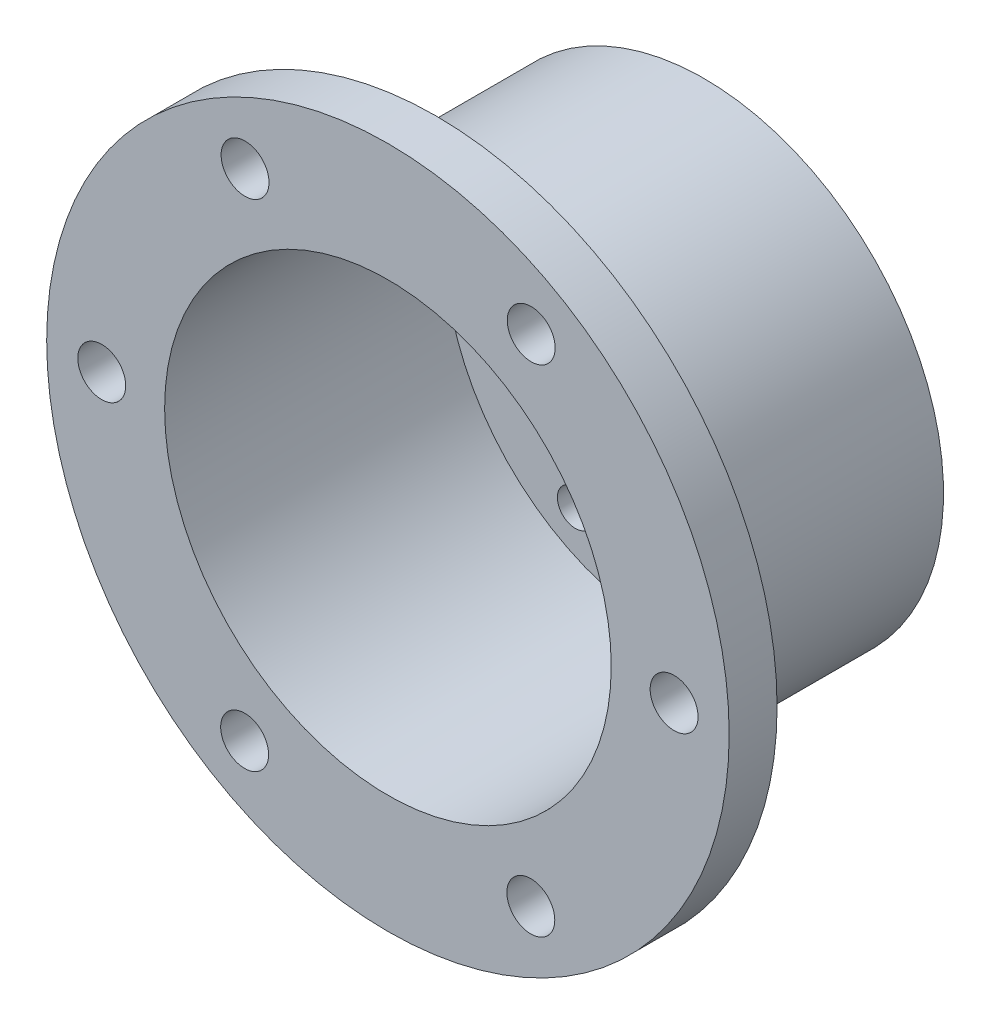
SolidWorks part; units mm, degrees
material "Resina de melamina"
ref_plane "Alzado" through (0, 0, 0) normal (0, 0, 1) x (1, 0, 0)
ref_plane "Planta" through (0, 0, 0) normal (0, 1, 0) x (1, 0, 0)
ref_plane "Vista lateral" through (0, 0, 0) normal (1, 0, 0) x (0, 0, -1)
sketch "Croquis1" plane through (0, 0, 0) normal (0, 0, 1) x (1, 0, 0)
  circle A0 centre (0, 0) radius 18.65
  circle A1 centre (0, 0) radius 21.4
  dimension "D1" = 37.3
  dimension "D2" = 42.8
extrude "Saliente-Extruir1" add sketch "Croquis1" along normal blind 26.4
sketch "Croquis2" plane through (0, 0, 0) normal (0, 0, -1) x (-1, 0, 0)
  circle A0 centre (0, 0) radius 18.65
  dimension "D1" = 37.3
extrude "Saliente-Extruir2" add sketch "Croquis2" against normal blind 3
sketch "Croquis3" plane through (0, 0, 26.4) normal (0, 0, 1) x (1, 0, 0)
  circle A0 centre (0, 0) radius 21.4
  circle A1 centre (0, 0) radius 28.5
  dimension "D1" = 57
extrude "Saliente-Extruir3" add sketch "Croquis3" against normal blind 4
sketch "Croquis4" plane through (0, 0, 0) normal (0, 0, -1) x (-1, 0, 0)
  line L0 (0, 0) -> (0, -7) construction
  line L1 (-13, 0) -> (-14, 0) construction
  line L2 (-14, 0) -> (-17, 0) construction
  circle A0 centre (0, -7) radius 6
  circle A9 centre (-15.5, 0) radius 1.5
  circle A10 centre (-7.75, 13.4234) radius 1.5
  circle A11 centre (7.75, 13.4234) radius 1.5
  circle A12 centre (15.5, 0) radius 1.5
  circle A13 centre (7.75, -13.4234) radius 1.5
  circle A14 centre (-7.75, -13.4234) radius 1.5
  dimension "D2" = 12
  dimension "D1" = 7
  dimension "D3" = 1
  dimension "D4" = 3
  dimension "D5" = 6
extrude "Cortar-Extruir1" cut sketch "Croquis4" against normal blind 3
sketch "Croquis6" plane through (0, 0, 26.4) normal (0, 0, 1) x (1, 0, 0)
  line L4 (0, 0) -> (23.9, -0.0193) construction
  circle A1 centre (11.9667, 20.6884) radius 2
  circle A8 centre (23.9, -0.0193) radius 2
  circle A10 centre (-11.9333, 20.7077) radius 2
  circle A16 centre (11.9333, -20.7077) radius 2
  circle A17 centre (-11.9667, -20.6884) radius 2
  circle A18 centre (-23.9, 0.0193) radius 2
  dimension "D1" = 23.9
  dimension "D2" = 4
  dimension "D3" = 6
extrude "Cortar-Extruir2" cut sketch "Croquis6" against normal through all
sketch "Croquis7" plane through (0, 0, 0) normal (0, 0, -1) x (-1, 0, 0)
  circle A0 centre (0, 0) radius 20
  circle A1 centre (0, 0) radius 21.4
  dimension "40" = 40
extrude "Cortar-Extruir3" cut sketch "Croquis7" against normal blind 22.4
